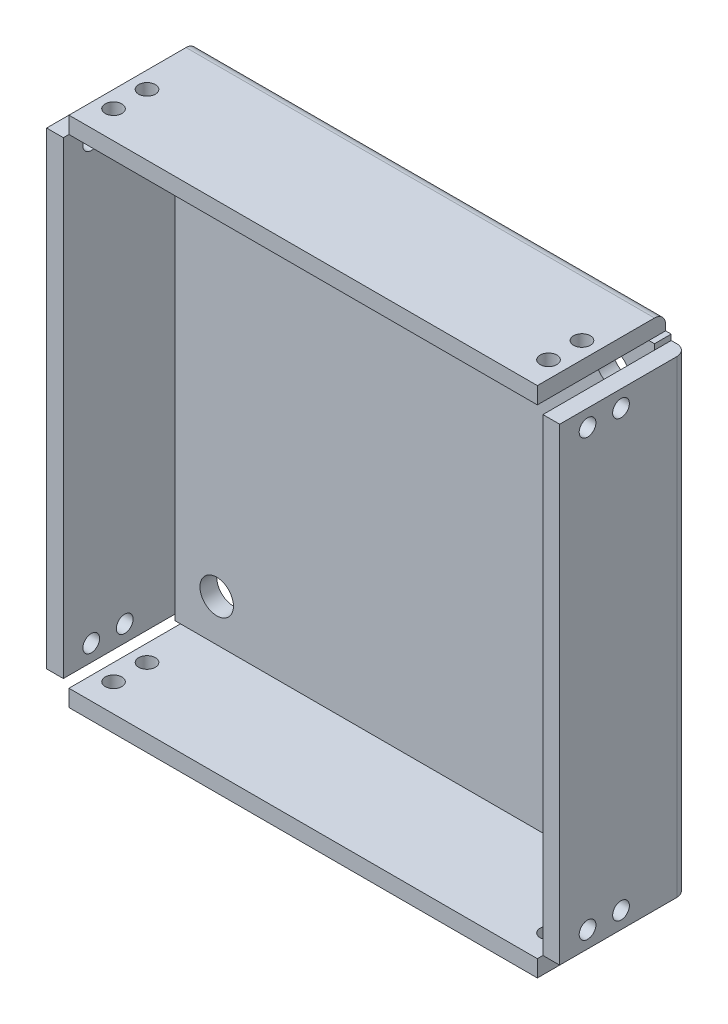
SolidWorks part; units mm, degrees
material "7075-T6, Plate (SS)"
ref_plane "Front Plane" through (0, 0, 0) normal (0, 0, 1) x (1, 0, 0)
ref_plane "Top Plane" through (0, 0, 0) normal (0, 1, 0) x (1, 0, 0)
ref_plane "Right Plane" through (0, 0, 0) normal (1, 0, 0) x (0, 0, -1)
sketch "Sketch1" plane through (0, 0, 0) normal (0, 0, 1) x (1, 0, 0)
  line L0 (-63.6939, 65.3178) -> (-63.6939, -20.6822)
  line L1 (-63.6939, -20.6822) -> (22.3061, -20.6822)
  line L2 (22.3061, -20.6822) -> (22.3061, 65.3178)
  line L3 (22.3061, 65.3178) -> (-63.6939, 65.3178)
  line L4 (21.3061, 68.3178) -> (-62.6939, 68.3178)
  line L5 (-62.6939, 68.3178) -> (-62.6939, 65.3178)
  line L6 (21.3061, 68.3178) -> (21.3061, 65.3178)
  line L7 (25.3061, 64.3178) -> (22.3061, 64.3178)
  line L8 (25.3061, 64.3178) -> (25.3061, -19.6822)
  line L9 (-66.6939, 64.3178) -> (-63.6939, 64.3178)
  line L10 (21.3061, -23.6822) -> (21.3061, -20.6822)
  line L11 (21.3061, -23.6822) -> (-62.6939, -23.6822)
  line L12 (-62.6939, -23.6822) -> (-62.6939, -20.6822)
  line L13 (-66.6939, -19.6822) -> (-66.6939, 64.3178)
  line L14 (-66.6939, -19.6822) -> (-63.6939, -19.6822)
  line L15 (25.3061, -19.6822) -> (22.3061, -19.6822)
  circle A0 centre (-56.1939, 57.8178) radius 3
  circle A1 centre (14.8061, 57.8178) radius 3
  circle A2 centre (14.8061, -13.1822) radius 3
  circle A3 centre (-56.1939, -13.1822) radius 3
  dimension "D7" = 6
  dimension "D8" = 6
  dimension "D9" = 6
  dimension "D10" = 6
  dimension "D2" = 92
  dimension "D3" = 84
  dimension "D4" = 84
  dimension "D5" = 3
  dimension "D6" = 3
  dimension "D11" = 7.5
  dimension "D12" = 7.5
  dimension "D13" = 7.5
  dimension "D14" = 7.5
  dimension "D15" = 7.5
  dimension "D16" = 7.5
  dimension "D17" = 7.5
  dimension "D18" = 7.5
  dimension "D19" = 1
  dimension "D20" = 86
  dimension "D21" = 84
  dimension "D22" = 84
  dimension "D23" = 1
  dimension "D24" = 1
  dimension "D25" = 1
  dimension "D26" = 86
  dimension "D27" = 3
extrude "Boss-Extrude1" add sketch "Sketch1" along normal blind 3 contours L2 L3 L0 L1 A3 A2 A1 A0 region at (-20.6939, 22.3178, 0)
extrude "Boss-Extrude3" add sketch "Sketch1<4>" along normal blind 23 contours L13 L0 | L3 | L11 L1 | L8 L2 region at (-65.1939, 22.3178, 0) region at (-20.6939, 66.8178, 0) region at (-20.6939, -22.1822, 0) region at (23.8061, 22.3178, 0)
sketch "Sketch1<4>" plane through (0, 0, 0) normal (0, 0, 1) x (1, 0, 0) same geometry as "Sketch1"
fillet "Fillet1" radius 2 4 edges at (-20.6939, -23.6822, 0) (-66.6939, 22.3178, 0) (-20.6939, 68.3178, 0) (25.3061, 22.3178, 0)
sketch "Sketch2" plane through (-66.6939, 0, 0) normal (-1, 0, 0) x (0, 0, 1)
  line L0 (23, -19.6822) -> (2, -19.6822) construction
  line L1 (23, -19.6822) -> (23, 64.3178) construction
  line L2 (23, 64.3178) -> (2, 64.3178) construction
  line L3 (0, -50.6) -> (0, 50.6) construction
  circle A0 centre (12, -16.6822) radius 1.5
  circle A1 centre (18, -16.6822) radius 1.5
  circle A2 centre (12, 61.3178) radius 1.5
  circle A3 centre (18, 61.3178) radius 1.5
  dimension "D1" = 3
  dimension "D2" = 3
  dimension "D7" = 3
  dimension "D8" = 3
  dimension "D3" = 3
  dimension "D4" = 3
  dimension "D5" = 5
  dimension "D6" = 6
  dimension "D9" = 3
  dimension "D10" = 3
  dimension "D11" = 5
  dimension "D12" = 6
extrude "Cut-Extrude1" cut sketch "Sketch2" against normal up to next
sketch "Sketch3" plane through (0, -23.6822, 0) normal (0, -1, 0) x (1, 0, 0)
  line L0 (21.3061, 23) -> (21.3061, 2) construction
  line L1 (-62.6939, 23) -> (-62.6939, 2) construction
  line L2 (21.3061, 23) -> (-62.6939, 23) construction
  circle A0 centre (18.3061, 12) radius 1.5
  circle A1 centre (18.3061, 18) radius 1.5
  circle A2 centre (-59.6939, 12) radius 1.5
  circle A3 centre (-59.6939, 18) radius 1.5
  dimension "D1" = 3
  dimension "D2" = 3
  dimension "D3" = 3
  dimension "D4" = 3
  dimension "D5" = 3
  dimension "D6" = 3
  dimension "D7" = 3
  dimension "D8" = 3
  dimension "D9" = 6
  dimension "D10" = 5
  dimension "D11" = 5
  dimension "D12" = 6
extrude "Cut-Extrude2" cut sketch "Sketch3" against normal up to next
sketch "Sketch4" plane through (25.3061, 0, 0) normal (1, 0, 0) x (0, 0, -1)
  line L0 (-23, 64.3178) -> (-2, 64.3178) construction
  line L1 (-23, 64.3178) -> (-23, -19.6822) construction
  line L2 (-23, -19.6822) -> (-2, -19.6822) construction
  circle A0 centre (-12, 61.3178) radius 1.5
  circle A1 centre (-18, 61.3178) radius 1.5
  circle A2 centre (-12, -16.6822) radius 1.5
  circle A3 centre (-18, -16.6822) radius 1.5
  dimension "D5" = 3
  dimension "D6" = 3
  dimension "D11" = 3
  dimension "D12" = 3
  dimension "D1" = 3
  dimension "D2" = 5
  dimension "D3" = 3
  dimension "D4" = 6
  dimension "D7" = 3
  dimension "D8" = 3
  dimension "D9" = 5
  dimension "D10" = 6
extrude "Cut-Extrude3" cut sketch "Sketch4" against normal up to next
sketch "Sketch5" plane through (0, 68.3178, 0) normal (0, 1, 0) x (1, 0, 0)
  line L0 (-62.6939, -23) -> (-62.6939, -2) construction
  line L2 (21.3061, -23) -> (-62.6939, -23) construction
  line L3 (21.3061, -23) -> (21.3061, -2) construction
  circle A0 centre (-59.6939, -12) radius 1.5
  circle A1 centre (-59.6939, -18) radius 1.5
  circle A2 centre (18.3061, -18) radius 1.5
  circle A3 centre (18.3061, -12) radius 1.5
  dimension "D5" = 3
  dimension "D6" = 3
  dimension "D11" = 3
  dimension "D12" = 3
  dimension "D1" = 3
  dimension "D2" = 3
  dimension "D3" = 5
  dimension "D4" = 6
  dimension "D7" = 3
  dimension "D8" = 3
  dimension "D9" = 6
  dimension "D10" = 5
extrude "Cut-Extrude4" cut sketch "Sketch5" against normal up to next
